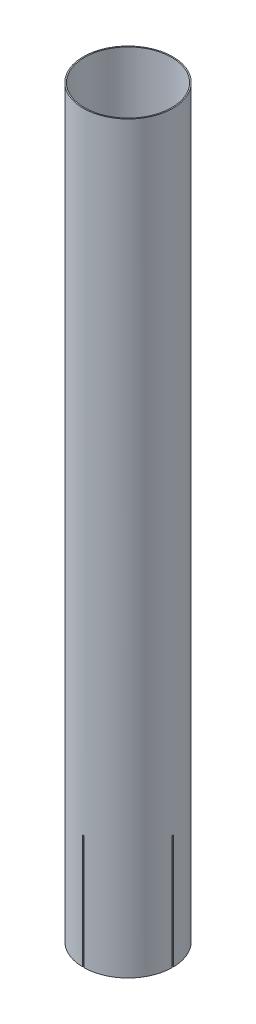
SolidWorks part; units mm, degrees
ref_plane "Front Plane" through (0, 0, 0) normal (0, 0, 1) x (1, 0, 0)
ref_plane "Top Plane" through (0, 0, 0) normal (0, 1, 0) x (1, 0, 0)
ref_plane "Right Plane" through (0, 0, 0) normal (1, 0, 0) x (0, 0, -1)
sketch "Sketch1" plane through (0, 0, 0) normal (0, 0, 1) x (1, 0, 0)
  line L0 (78.2, 0) -> (78.2, 1300)
  line L1 (0, 0) -> (0, 2000) construction
  line L9 (76.2, 0) -> (76.2, 1300)
  line L10 (78.2, 0) -> (76.2, 0)
  line L11 (78.2, 1300) -> (76.2, 1300)
  point P7 (65, 1600)
  point P8 (-1029.1667, 1600)
  point P9 (-9.3208, 1996.3774)
  dimension "D1" = 1300
  dimension "D2" = 76.2
  dimension "D3" = 2000
  dimension "D4" = 2
revolve "Revolve1" add sketch "Sketch1" angle 360 about L1
sketch "Sketch2" plane through (0, 0, 0) normal (0, 0, 1) x (1, 0, 0)
  line L0 (-185.2, 150) -> (-185.2, 0)
  line L1 (-185.2, 0) -> (-78.2, 0)
  line L2 (-78.2, 0) -> (-78.2, 200) construction
  line L3 (-78.2, 200) -> (-185.2, 150)
  line L4 (-78.2, 0) -> (0, 0)
  line L5 (-78.2, 200) -> (0, 200)
  line L6 (0, 0) -> (0, 200)
  dimension "D1" = 200
  dimension "D2" = 150
  dimension "D3" = 107
extrude "Cut-Extrude1" cut sketch "Sketch2" against normal blind 1.5 and the other way blind 1.5
pattern_circular "CirPattern1" count 4 over 360 about axis through (0, 0, 0) along (0, -1, 0) of "Cut-Extrude1"
